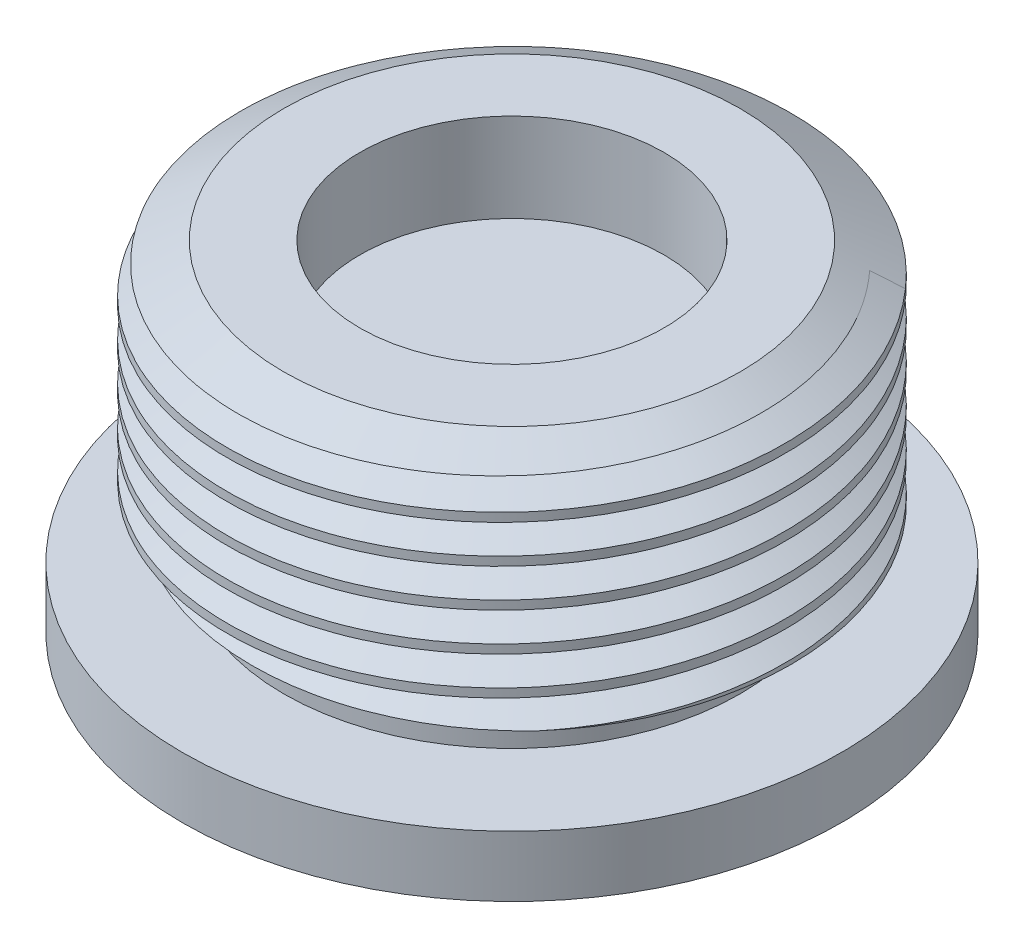
SolidWorks part; units mm, degrees
ref_plane "Front Plane" through (0, 0, 0) normal (0, 0, 1) x (1, 0, 0)
ref_plane "Top Plane" through (0, 0, 0) normal (0, 1, 0) x (1, 0, 0)
ref_plane "Right Plane" through (0, 0, 0) normal (1, 0, 0) x (0, 0, -1)
sketch "Croquis1" plane through (0, 0, 0) normal (0, 1, 0) x (1, 0, 0)
  circle A0 centre (0, 0) radius 13
  dimension "D1" = 26
extrude "Saliente-Extruir1" add sketch "Croquis1" along normal blind 2.4
sketch "Croquis2" plane through (0, 2.4, 0) normal (0, 1, 0) x (1, 0, 0)
  circle A0 centre (0, 0) radius 9
  dimension "D1" = 18
extrude "Saliente-Extruir2" add sketch "Croquis2" along normal blind 2
sketch "Croquis3" plane through (0, 4.4, 0) normal (0, 1, 0) x (1, 0, 0)
  circle A0 centre (0, 0) radius 11
  dimension "D1" = 22
extrude "Saliente-Extruir3" add sketch "Croquis3" along normal blind 9
sketch "Croquis4" plane through (0, 13.4, 0) normal (0, 1, 0) x (1, 0, 0)
  circle A0 centre (0, 0) radius 11
curve "Hélice/Espiral1" pitch 1.5 height 9 radius 11 centre (0, 13.4, 0) axis (0, -1, 0) start towards (0, 0, 1)
sketch "Croquis6" plane through (0, 0, 0) normal (0, 0, 1) x (1, 0, 0)
  line L0 (-11, 13.4) -> (-11, 4.4) construction
  line L1 (-10, 13.4) -> (-11.5, 14.266)
  line L2 (-11.5, 14.266) -> (-11.5, 12.534)
  line L3 (-11.5, 12.534) -> (-10, 13.4)
  circle A0 centre (-11, 13.4) radius 0.5 construction
  spline S0 degree 3 poles (-11, 13.4) (-11, 13.369) (-10.4273, 13.3062) (-7.9807, 13.2125) (-4.3191, 13.1187) (0, 13.025) (4.3191, 12.9312) (7.9807, 12.8375) (10.4273, 12.7437) (11.2864, 12.65) (10.4273, 12.5562) (7.9807, 12.4625) (3.0986, 12.3375) (-3.0986, 12.2125) (-7.9807, 12.0875) (-10.4273, 11.9937) (-11.2864, 11.9) (-10.4273, 11.8062) (-7.9807, 11.7125) (-3.0986, 11.5875) (3.0986, 11.4625) (7.9807, 11.3375) (10.4273, 11.2437) (11.2864, 11.15) (10.4273, 11.0562) (7.9807, 10.9625) (3.0986, 10.8375) (-3.0986, 10.7125) (-7.9807, 10.5875) (-10.4273, 10.4938) (-11.2864, 10.4) (-10.4273, 10.3062) (-7.9807, 10.2125) (-3.0986, 10.0875) (3.0986, 9.9625) (7.9807, 9.8375) (10.4273, 9.7437) (11.2864, 9.65) (10.4273, 9.5562) (7.9807, 9.4625) (3.0986, 9.3375) (-3.0986, 9.2125) (-7.9807, 9.0875) (-10.4273, 8.9937) (-11.2864, 8.9) (-10.4273, 8.8062) (-7.9807, 8.7125) (-3.0986, 8.5875) (3.0986, 8.4625) (7.9807, 8.3375) (10.4273, 8.2437) (11.2864, 8.15) (10.4273, 8.0562) (7.9807, 7.9625) (3.0986, 7.8375) (-3.0986, 7.7125) (-7.9807, 7.5875) (-10.4273, 7.4937) (-11.2864, 7.4) (-10.4273, 7.3062) (-7.9807, 7.2125) (-3.0986, 7.0875) (3.0986, 6.9625) (7.9807, 6.8375) (10.4273, 6.7437) (11.2864, 6.65) (10.4273, 6.5562) (7.9807, 6.4625) (3.0986, 6.3375) (-3.0986, 6.2125) (-7.9807, 6.0875) (-10.4273, 5.9938) (-11.2864, 5.9) (-10.4273, 5.8063) (-7.9807, 5.7125) (-3.0986, 5.5875) (3.0986, 5.4625) (7.9807, 5.3375) (10.4273, 5.2438) (11.2864, 5.15) (10.4273, 5.0563) (7.9807, 4.9625) (4.3191, 4.8688) (0, 4.775) (-4.3191, 4.6813) (-7.9807, 4.5875) (-10.4273, 4.4938) (-11, 4.431) (-11, 4.4) knots 0 0 0 0 0.010417 0.020833 0.03125 0.041667 0.052083 0.0625 0.072917 0.083333 0.09375 0.104167 0.114583 0.135417 0.145833 0.15625 0.166667 0.177083 0.1875 0.197917 0.21875 0.229167 0.239583 0.25 0.260417 0.270833 0.28125 0.302083 0.3125 0.322917 0.333333 0.34375 0.354167 0.364583 0.385417 0.395833 0.40625 0.416667 0.427083 0.4375 0.447917 0.46875 0.479167 0.489583 0.5 0.510417 0.520833 0.53125 0.552083 0.5625 0.572917 0.583333 0.59375 0.604167 0.614583 0.635417 0.645833 0.65625 0.666667 0.677083 0.6875 0.697917 0.71875 0.729167 0.739583 0.75 0.760417 0.770833 0.78125 0.802083 0.8125 0.822917 0.833333 0.84375 0.854167 0.864583 0.885417 0.895833 0.90625 0.916667 0.927083 0.9375 0.947917 0.958333 0.96875 0.979167 0.989583 1 1 1 1 construction
  dimension "D1" = 1
sweep "Cortar-Barrer1" cut profiles "Croquis6" path "Hélice/Espiral1" align with end faces yes
sketch "Croquis7" plane through (0, 13.4, 0) normal (0, 1, 0) x (1, 0, 0)
  circle A0 centre (0, 0) radius 6
  dimension "D1" = 12
extrude "Cortar-Extruir1" cut sketch "Croquis7" against normal blind 3.5
sketch "Croquis8" plane through (0, 0, 0) normal (0, -1, 0) x (1, 0, 0)
  line L1 (4.3296, 0) -> (3.0615, 3.0615)
  line L2 (3.0615, 3.0615) -> (0, 4.3296)
  line L3 (0, 4.3296) -> (-3.0615, 3.0615)
  line L4 (-3.0615, 3.0615) -> (-4.3296, 0)
  line L5 (-4.3296, 0) -> (-3.0615, -3.0615)
  line L6 (-3.0615, -3.0615) -> (0, -4.3296)
  line L7 (0, -4.3296) -> (3.0615, -3.0615)
  line L8 (3.0615, -3.0615) -> (4.3296, 0)
  circle A0 centre (0, 0) radius 4 construction
  dimension "D1" = 4
extrude "Cortar-Extruir2" cut sketch "Croquis8" against normal blind 6 contours L1 L2 L3 L4 L5 L6 L7 L8
sketch "Croquis10" plane through (0, 0, 0) normal (0, -1, 0) x (1, 0, 0)
  circle A0 centre (0, 0) radius 4.3296
sketch "Croquis11" plane through (0, 0, 0) normal (0, 0, 1) x (1, 0, 0)
  line L4 (9, 13.4) -> (12, 11.6679)
  line L5 (12, 11.6679) -> (12, 15.1321)
  line L6 (12, 15.1321) -> (9, 13.4)
  circle A0 centre (11, 13.4) radius 1 construction
  dimension "D1" = 2
sketch "Croquis12" plane through (0, 13.4, 0) normal (0, 1, 0) x (1, 0, 0)
  circle A0 centre (0, 0) radius 11
  dimension "D1" = 22
sweep "Cortar-Barrer3" cut profiles "Croquis11" path "Croquis12"
sketch "Croquis13" plane through (0, 0, 0) normal (0, 0, 1) x (1, 0, 0)
  line L0 (-4.3296, 0) -> (4.3296, 0) construction
  line L4 (-4.3065, 0) -> (-3.8565, -0.2598)
  line L5 (-3.8565, -0.2598) -> (-3.8565, 0.2598)
  line L6 (-3.8565, 0.2598) -> (-4.3065, 0)
  circle A0 centre (-4.0065, 0) radius 0.15 construction
  dimension "D1" = 0.3
sweep "Cortar-Barrer4" cut profiles "Croquis13" path "Croquis10"
